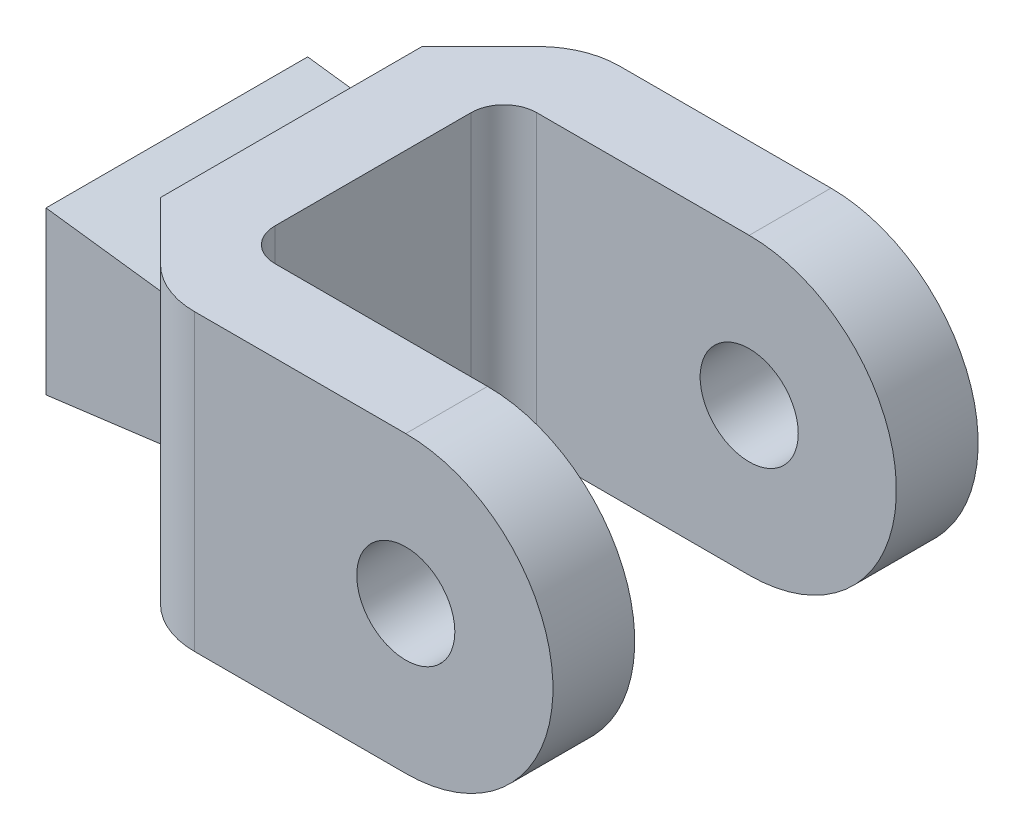
SolidWorks part; units mm, degrees
ref_plane "Front Plane" through (0, 0, 0) normal (0, 0, 1) x (1, 0, 0)
ref_plane "Top Plane" through (0, 0, 0) normal (0, 1, 0) x (1, 0, 0)
ref_plane "Right Plane" through (0, 0, 0) normal (1, 0, 0) x (0, 0, -1)
sketch "Sketch1" plane through (0, 0, 0) normal (0, 0, 1) x (1, 0, 0)
  line L0 (-2.2687, 0) -> (4.5375, 0) construction
  line L4 (-1.75, -2.475) -> (-1.75, 2.475)
  line L5 (1.4583, -2.0625) -> (-1.75, 2.475) construction
  line L6 (1.4583, 2.0625) -> (-1.75, -2.475) construction
  line L7 (-1.75, -2.475) -> (1.75, -2.025)
  line L8 (-1.75, 2.475) -> (1.75, 2.025)
  line L21 (1.75, 2.025) -> (1.75, 4.5)
  line L22 (4.25, -4.5) -> (1.75, -4.5)
  line L25 (4.25, -4.5) -> (4.25, 4.5)
  line L26 (4.25, 4.5) -> (1.75, 4.5)
  line L27 (1.75, -4.5) -> (1.75, -2.025)
  line L28 (4.25, -4.5) -> (1.75, 4.5) construction
  line L29 (4.25, 4.5) -> (1.75, -4.5) construction
  point P0 (0, 0)
  point P2 (3, 0)
  point P3 (3, 0)
  point P6 (1.75, 2.025)
  point P9 (1.75, -2.025)
  dimension "D1" = 4.95
  dimension "D2" = 2.5
  dimension "D3" = 9
extrude "Boss-Extrude1" add sketch "Sketch1" along normal blind 8 contours L8 L21 L26 L25 L22 L27 L7 L4
sketch "Sketch2" plane through (0, 0, 0) normal (0, 0, 1) x (1, 0, 0)
  line L0 (-1.75, 0) -> (25.7432, 0) construction
  line L1 (-1.75, -2.475) -> (-1.75, 2.475) construction
  line L3 (11.75, -4.5) -> (1.75, -4.5)
  line L5 (11.75, 4.5) -> (1.75, 4.5)
  line L6 (1.75, -4.5) -> (1.75, 4.5)
  line L7 (15.0971, -3.0078) -> (1.75, 4.5) construction
  line L8 (15.0971, 3.0078) -> (1.75, -4.5) construction
  line L11 (1.75, -4.5) -> (1.75, -2.025) construction
  arc A0 (11.75, -4.5) -> (11.75, 4.5) centre (11.75, 0) ccw
  circle A1 centre (11.75, 0) radius 1.5
  circle A2 centre (11.75, 0) radius 6.5 construction
  point P5 (9.75, 0)
  point P7 (16.25, 0)
  dimension "D3" = 3
  dimension "D4" = 13
  dimension "D1" = 14.5
  dimension "D2" = 9
extrude "Boss-Extrude3" add sketch "Sketch2" against normal blind 2.5
sketch "Sketch5" plane through (0, 0, 0) normal (0, 1, 0) x (1, 0, 0)
  line L0 (4.25, 0) -> (4.25, 4.091) construction
  line L1 (11.75, 2.5) -> (1.75, 2.5) construction
  line L2 (1.75, 0) -> (4.25, 2.5)
  line L3 (4.25, 2.5) -> (1.75, 2.5)
  line L4 (1.75, 2.5) -> (1.75, 0)
  point P3 (4.25, 2.5)
extrude "Cut-Extrude2" cut sketch "Sketch5" against normal through all and the other way through all
fillet "Fillet5" radius 1 1 edges at (4.25, 0, 0)
fillet "Fillet6" radius 2.5 1 edges at (4.25, 0, -2.5)
ref_plane "Plane1" through (0, 0, 4) normal (0, 0, -1) x (-1, 0, 0)
mirror "Mirror2" about plane through (0, 0, 4) normal (0, 0, -1) of "Cut-Extrude2", "Fillet6", "Fillet5", "Boss-Extrude3"
